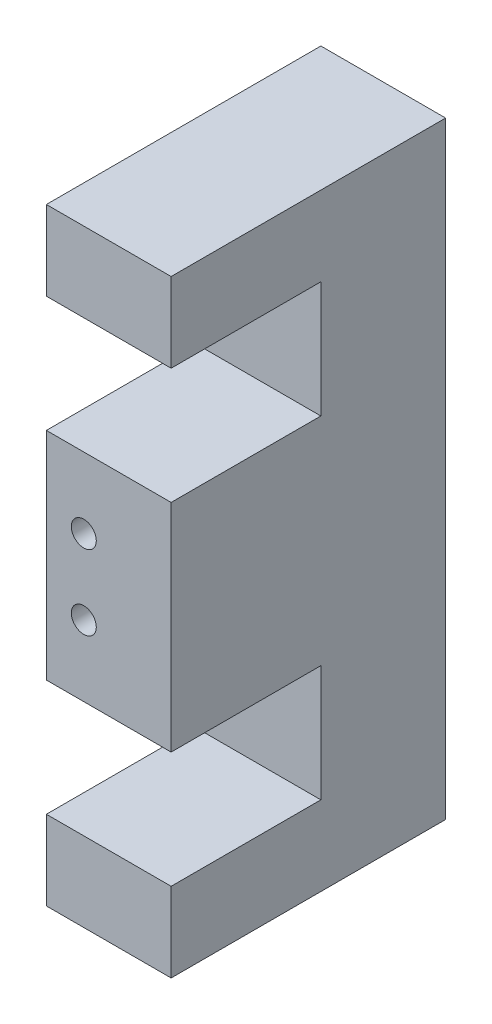
SolidWorks part; units mm, degrees
note: The reader was unsure of these and kept them because the rebuilt part matched: shared geometry of "Sketch2<4>", "Sketch3<3>".
ref_plane "Front Plane" through (0, 0, 0) normal (0, 0, 1) x (1, 0, 0)
ref_plane "Top Plane" through (0, 0, 0) normal (0, 1, 0) x (1, 0, 0)
ref_plane "Right Plane" through (0, 0, 0) normal (1, 0, 0) x (0, 0, -1)
sketch "Sketch2" plane through (0, 0, 0) normal (0, 0, 1) x (1, 0, 0)
  line L0 (28.45, 5.9146) -> (28.45, -39.7529) construction
  line L1 (-50.8, 5.9146) -> (32.8, 5.9146) construction
  line L2 (32.8, -39.7529) -> (-50.8, -39.7529) construction
  line L3 (36.8, 14) -> (52.8, 14) construction
  line L4 (34.8, 14) -> (22.1, 14)
  line L5 (34.8, 14) -> (34.8, -47.8383)
  line L6 (34.8, -47.8383) -> (22.1, -47.8383)
  line L7 (22.1, 14) -> (22.1, -47.8383)
  line L8 (34.8, 14) -> (22.1, -47.8383) construction
  line L9 (34.8, -47.8383) -> (22.1, 14) construction
  line L10 (32.8, -5.9146) -> (-50.8, -5.9146) construction
  line L11 (22.1, 5.9146) -> (34.8, 5.9146)
  line L12 (22.1, 5.9146) -> (22.1, -5.9146)
  line L13 (22.1, -5.9146) -> (34.8, -5.9146)
  line L14 (34.8, 5.9146) -> (34.8, -5.9146)
  line L15 (-50.8, -27.9238) -> (32.8, -27.9238) construction
  line L16 (21.5073, -27.9238) -> (34.8, -27.9238)
  line L17 (21.5073, -27.9238) -> (21.5073, -39.7529)
  line L18 (21.5073, -39.7529) -> (34.8, -39.7529)
  line L19 (34.8, -27.9238) -> (34.8, -39.7529)
  line L20 (34.8, 7.9146) -> (34.8, 12) construction
  point P6 (28.45, -16.9192)
  point P25 (21.5073, -27.9238)
  point P26 (27.8647, -39.7529)
  line M33 (34.8, 12) -> (34.8, 7.9146)
  arc M34 (34.8, 7.9146) -> (32.8, 5.9146) centre (32.8, 7.9146) cw
  line M35 (32.8, 5.9146) -> (-50.8, 5.9146)
  line M37 (-50.8, -5.9146) -> (32.8, -5.9146)
  arc M38 (32.8, -5.9146) -> (34.8, -7.9146) centre (32.8, -7.9146) cw
  line M39 (34.8, -7.9146) -> (34.8, -12)
  dimension "D1" = 12.7
extrude "Boss-Extrude1" add sketch "Sketch2" against normal blind 12.7 from surface at -4 contours L4 L7 L5 M35 M34 M33 | L13 L5 L11 L7 M37 M35 | L7 L16 L5 M39 M38 M37 | L7 L18 L5 L16 | L18 L7 L6 L5 | L11 L5 M34 | L13 L5 M38
extrude "Boss-Extrude3" add sketch "Sketch2<4>" along normal blind 15.24 from surface contours L4 L7 L5 M35 M34 M33 | L11 L5 M34 | L7 L16 L5 M39 M38 M37 | L13 L5 M38 | L18 L7 L6 L5
sketch "Sketch2<4>" plane through (0, 0, 0) normal (0, 0, 1) x (1, 0, 0) same geometry as "Sketch2"
sketch "Sketch3" plane through (0, 0, -16.7) normal (0, 0, -1) x (-1, 0, 0)
  line L0 (-34.8, -16.9192) -> (-22.1, -16.9192) construction
  line L1 (-34.8, 14) -> (-34.8, -47.8383) construction
  line L2 (-22.1, 14) -> (-22.1, -47.8383) construction
  line L3 (-25.91, -13.1092) -> (-25.91, -20.7292) construction
  circle A0 centre (-29.72, -16.9192) radius 1.778
  circle A2 centre (-25.91, -13.1092) radius 1.27
  circle A3 centre (-25.91, -20.7292) radius 1.27
  point P13 (-25.91, -16.9192)
  dimension "D1" = 3.556
  dimension "D2" = 2.54
  dimension "D3" = 3.81
  dimension "D4" = 7.62
  dimension "D5" = 5.08
extrude "Cut-Extrude1" cut sketch "Sketch3" against normal blind 7.62 contours A0
extrude "Cut-Extrude2" cut sketch "Sketch3<3>" against normal through all contours A2 | A3
sketch "Sketch3<3>" plane through (0, 0, -16.7) normal (0, 0, -1) x (-1, 0, 0) same geometry as "Sketch3"
